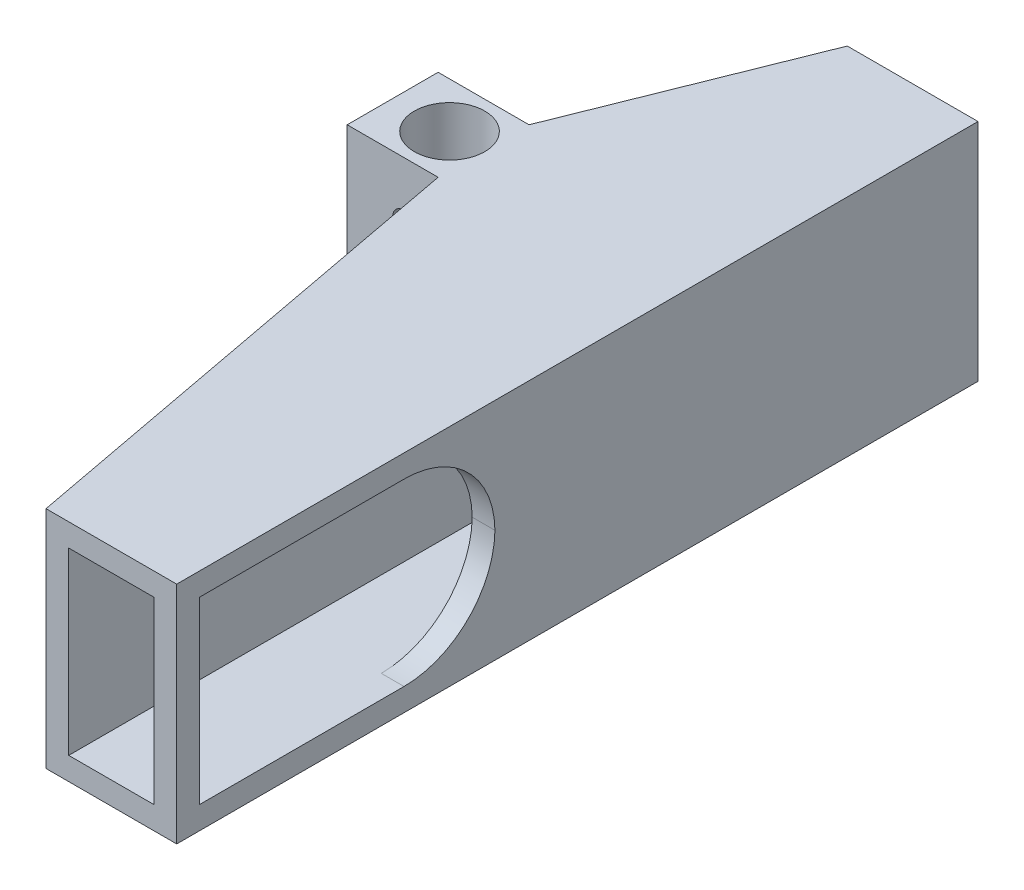
SolidWorks part; units mm, degrees
ref_plane "Alzado" through (0, 0, 0) normal (1, 0, 0) x (0, 1, 0)
ref_plane "Planta" through (0, 0, 0) normal (0, 0, 1) x (0, 1, 0)
ref_plane "Vista lateral" through (0, 0, 0) normal (0, 1, 0) x (-1, 0, 0)
sketch "Croquis1" plane through (0, 0, 0) normal (0, 0, 1) x (0, 1, 0)
  line L1 (-9.9, -5.75) -> (9.9, -5.75)
  line L2 (-9.9, -5.75) -> (-9.9, 5.75)
  line L3 (-9.9, 5.75) -> (9.9, 5.75)
  line L4 (9.9, -5.75) -> (9.9, 5.75)
  line L5 (-9.9, -5.75) -> (9.9, 5.75) construction
  line L6 (-9.9, 5.75) -> (9.9, -5.75) construction
  point P0 (0, 0)
  dimension "D1" = 19.8
  dimension "D2" = 11.5
extrude "Saliente-Extruir1" add sketch "Croquis1" along normal blind 70.5 contours L2 L1 L4 L3
shell "Vaciado1" thickness 2 removed face at (0, 0, 70.5)
sketch "Croquis3" plane through (0, 0, 70.5) normal (0, 0, 1) x (1, 0, 0)
  line L0 (3.75, 7.9) -> (5.75, 7.9)
  line L1 (5.75, -9.9) -> (5.75, 9.9) construction
  line L2 (3.75, -7.9) -> (5.75, -7.9)
sketch "Croquis4" plane through (5.75, 0, 0) normal (1, 0, 0) x (0, 1, 0)
  line L0 (-7.9, 70.5) -> (7.9, 70.5)
  line L1 (-7.9, 70.5) -> (-7.9, 42.5)
  line L2 (7.9, 70.5) -> (7.9, 42.5)
  line L3 (-7.9, 42.5) -> (7.9, 42.5)
  dimension "D1" = 15.8
  dimension "D2" = 28
extrude "Cortar-Extruir1" cut sketch "Croquis4" against normal blind 2
fillet "Redondeo1" radius 8 2 edges at (4.75, 7.9, 42.5) (4.75, -7.9, 42.5)
sketch "Croquis5" plane through (5.75, 0, 0) normal (1, 0, 0) x (0, 1, 0)
  line L0 (-7.9, 70.5) -> (-7.9, 68.5)
  line L1 (-7.9, 70.5) -> (7.9, 70.5)
  line L2 (-7.9, 68.5) -> (7.9, 68.5)
  line L3 (7.9, 70.5) -> (7.9, 68.5)
  line L4 (-7.9, 70.5) -> (-7.9, 50.5) construction
  dimension "D1" = 15.8
  dimension "D2" = 2
extrude "Saliente-Extruir2" add sketch "Croquis5" against normal blind 2 contours L0 L1 L3 L2
sketch "Croquis6" plane through (-5.75, 0, 0) normal (-1, 0, 0) x (0, -1, 0)
  line L0 (-9.9, 20) -> (9.9, 20)
  line L1 (-9.9, 20) -> (-9.9, 28)
  line L2 (9.9, 20) -> (9.9, 28)
  line L3 (-9.9, 28) -> (9.9, 28)
  line L7 (9.9, 0) -> (-9.9, 0) construction
  line L8 (-9.9, 70.5) -> (-9.9, 0) construction
  line L9 (9.9, 70.5) -> (9.9, 0) construction
  dimension "D1" = 8
  dimension "D2" = 20
extrude "Saliente-Extruir4" add sketch "Croquis6" along normal blind 16
sketch "Croquis8" plane through (0, 0, 28) normal (0, 0, 1) x (1, 0, 0)
  circle A0 centre (-16.75, 4.9) radius 1
  circle A1 centre (-16.75, -4.9) radius 1
  dimension "D4" = 2
  dimension "D5" = 2
extrude "Cortar-Extruir3" cut sketch "Croquis8" against normal blind 10 contours A0 | A1 region at (-16.75, 4.9, 28)
sketch "Croquis9" plane through (0, -9.9, 0) normal (0, -1, 0) x (1, 0, 0)
  line L0 (-5.75, 70.5) -> (-13.75, 28)
  line L1 (-21.75, 28) -> (-5.75, 28) construction
  line L2 (-13.75, 28) -> (-5.75, 28)
  line L3 (-5.75, 28) -> (-5.75, 70.5)
  line L4 (-5.75, 0) -> (-13.75, 20)
  line L5 (-21.75, 20) -> (-5.75, 20) construction
  line L6 (-13.75, 20) -> (-5.75, 20)
  line L7 (-5.75, 20) -> (-5.75, 0)
  point P12 (0, 0)
  point P15 (-13.75, 28)
extrude "Saliente-Extruir5" add sketch "Croquis9" against normal blind 19.8
sketch "Croquis10" plane through (0, -9.9, 0) normal (0, -1, 0) x (1, 0, 0)
  line L0 (-21.75, 20) -> (-21.75, 28) construction
  circle A0 centre (-16.7453, 24) radius 3.1
  point P2 (0, 0)
  point P5 (-21.75, 24)
  dimension "D1" = 6.2
  dimension "D2" = 5.0047
extrude "Cortar-Extruir4" cut sketch "Croquis10" against normal blind 19.8
fillet "Redondeo2" [suppressed] radius 10
equation "\"15.8mm.\"=19.8"
